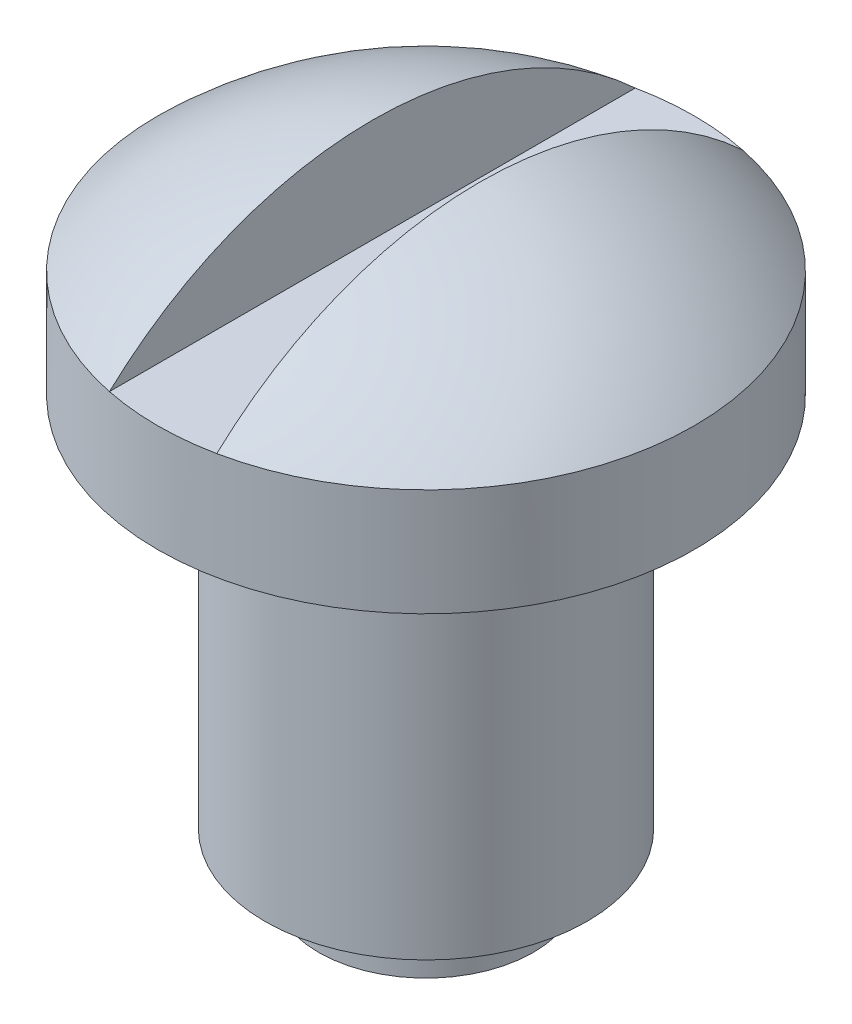
SolidWorks part; units mm, degrees
ref_plane "Front Plane" through (0, 0, 0) normal (0, 0, 1) x (1, 0, 0)
ref_plane "Top Plane" through (0, 0, 0) normal (0, 1, 0) x (1, 0, 0)
ref_plane "Right Plane" through (0, 0, 0) normal (1, 0, 0) x (0, 0, -1)
sketch "Sketch1" plane through (0, 0, 0) normal (0, 0, 1) x (1, 0, 0)
  line L0 (0, 0) -> (-2, 0)
  line L1 (-2, 0) -> (-2, 1)
  line L2 (-2, 1) -> (-3, 1)
  line L3 (-3, 1) -> (-3, 8)
  line L4 (-3, 8) -> (-5, 8)
  line L5 (-5, 8) -> (-5, 10)
  line L6 (0, 10) -> (-5, 10)
  line L7 (0, 0) -> (0, 10)
  dimension "D1" = 5
revolve "Revolve3" add sketch "Sketch1" angle 360 about L7
sketch "Sketch3" plane through (0, 10, 0) normal (0, 1, 0) x (1, 0, 0)
  line L0 (0, 5.5418) -> (0, -5.4095) construction
  line L2 (-1, 5.6007) -> (1, 5.6007)
  line L3 (-1, 5.6007) -> (-1, -5.6007)
  line L4 (-1, -5.6007) -> (1, -5.6007)
  line L5 (1, 5.6007) -> (1, -5.6007)
  line L6 (-1, 5.6007) -> (1, -5.6007) construction
  line L7 (-1, -5.6007) -> (1, 5.6007) construction
  point P3 (0, 0)
  dimension "D1" = 2
dome "Dome4" faces to dome 1 distance 2 reverse direction no elliptical dome no face at (0, 10, -5) parameters "D1"=2
extrude "Extrude3" cut sketch "Sketch3" along normal blind 2
